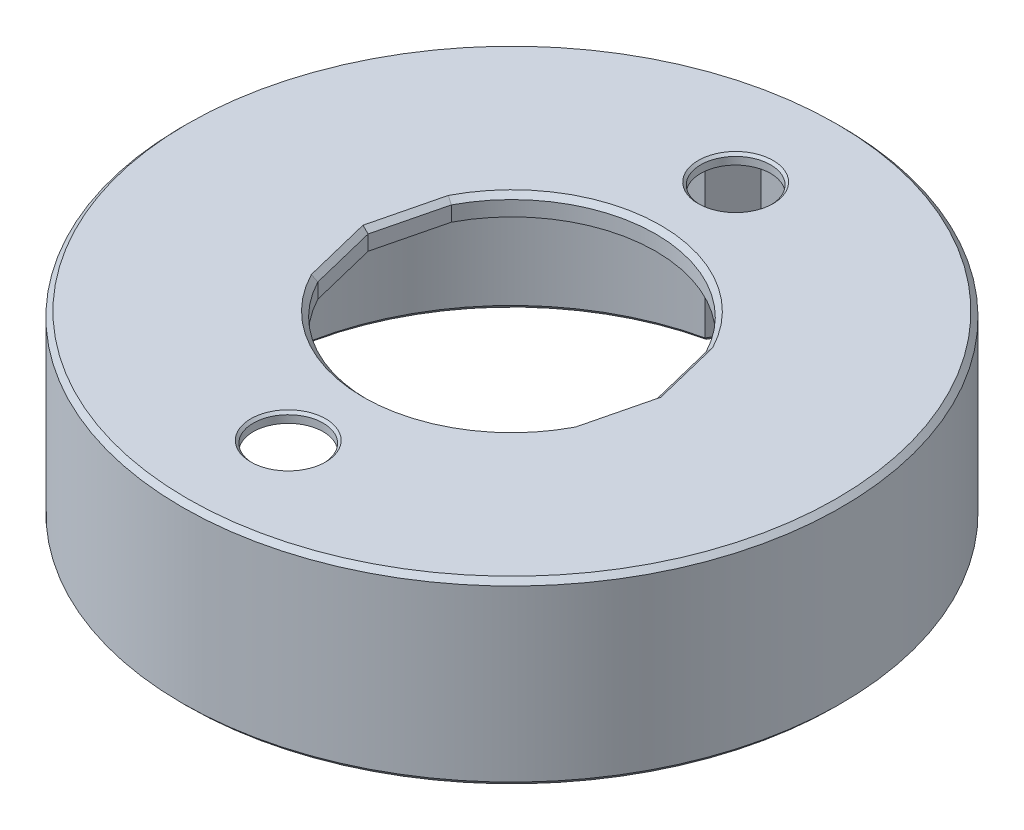
SolidWorks part; units mm, degrees
ref_plane "Front Plane" through (0, 0, 0) normal (0, 0, 1) x (1, 0, 0)
ref_plane "Top Plane" through (0, 0, 0) normal (0, 1, 0) x (1, 0, 0)
ref_plane "Right Plane" through (0, 0, 0) normal (1, 0, 0) x (0, 0, -1)
sketch "Sketch1" plane through (0, 0, 0) normal (0, 1, 0) x (1, 0, 0)
  circle A0 centre (0, 0) radius 12.73
  circle A1 centre (0, 0) radius 16.5
  dimension "D1" = 3.77
  dimension "D2" = 33
extrude "Boss-Extrude1" add sketch "Sketch1" along normal blind 8
sketch "Sketch2" plane through (0, 8, 0) normal (0, 1, 0) x (1, 0, 0)
  circle A0 centre (0, 0) radius 16.5
extrude "Boss-Extrude2" add sketch "Sketch2" along normal blind 1
sketch "Sketch3" plane through (0, 9, 0) normal (0, 1, 0) x (1, 0, 0)
  line L0 (0, 13) -> (0, 11.2)
  line L1 (0, -13) -> (0, -11.2)
  line L2 (0, -13) -> (4, -13)
  line L3 (0, -13) -> (-4, -13)
  line L4 (0, 13) -> (-4, 13)
  line L5 (0, 13) -> (4, 13)
  line L6 (-7.2, 0) -> (-4, -13)
  line L7 (7.2, 0) -> (4, -13)
  line L8 (-4, 13) -> (-7.2, 0)
  line L9 (4, 13) -> (7.2, 0)
  circle A0 centre (0, 0) radius 7.2
  circle A4 centre (0, 11.2) radius 1.75
  circle A5 centre (0, -11.2) radius 1.75
  dimension "D1" = 14.4
  dimension "D7" = 1.8
  dimension "D8" = 3.5
  dimension "D9" = 1.8
  dimension "D10" = 3.5
  dimension "D2" = 13
  dimension "D3" = 13
  dimension "D4" = 4
  dimension "D5" = 4
  dimension "D6" = 4
extrude "Cut-Extrude1" cut sketch "Sketch3" against normal blind 12 contours L9 A0 L8 L6 L7 | A4 | A5 region at (1.2024, 9, -12.4024) region at (0, 9, 0) region at (-1.2024, 9, 9.9976)
sketch "Sketch4" plane through (0, 8, 0) normal (0, -1, 0) x (1, 0, 0)
  line L1 (3.4641, 11.2) -> (1.7321, 14.2)
  line L2 (1.7321, 14.2) -> (-1.7321, 14.2)
  line L3 (-1.7321, 14.2) -> (-3.4641, 11.2)
  line L4 (-3.4641, 11.2) -> (-1.7321, 8.2)
  line L5 (-1.7321, 8.2) -> (1.7321, 8.2)
  line L6 (1.7321, 8.2) -> (3.4641, 11.2)
  circle A0 centre (0, 11.2) radius 3 construction
  dimension "D1" = 6
extrude "Cut-Extrude2" cut sketch "Sketch4" along normal blind 12
sketch "Sketch5" plane through (0, 8, 0) normal (0, -1, 0) x (1, 0, 0)
  line L1 (3.4416, 11.2) -> (1.7208, 14.1806)
  line L2 (1.7208, 14.1806) -> (-1.7208, 14.1806)
  line L3 (-1.7208, 14.1806) -> (-3.4416, 11.2)
  line L4 (-3.4416, 11.2) -> (-1.7208, 8.2194)
  line L5 (-1.7208, 8.2194) -> (1.7208, 8.2194)
  line L6 (1.7208, 8.2194) -> (3.4416, 11.2)
  circle A0 centre (0, 11.2) radius 2.9806 construction
extrude "Cut-Extrude3" cut sketch "Sketch5" against normal blind 0.5
sketch "Sketch6" plane through (0, 8, 0) normal (0, -1, 0) x (1, 0, 0)
  line L1 (3.4641, -11.2) -> (1.7321, -8.2)
  line L2 (1.7321, -8.2) -> (-1.7321, -8.2)
  line L3 (-1.7321, -8.2) -> (-3.4641, -11.2)
  line L4 (-3.4641, -11.2) -> (-1.7321, -14.2)
  line L5 (-1.7321, -14.2) -> (1.7321, -14.2)
  line L6 (1.7321, -14.2) -> (3.4641, -11.2)
  circle A0 centre (0, -11.2) radius 3 construction
  dimension "D1" = 6
extrude "Cut-Extrude4" cut sketch "Sketch6" along normal blind 17.5
sketch "Sketch7" plane through (0, 8, 0) normal (0, -1, 0) x (1, 0, 0)
  line L1 (3.4876, -11.2) -> (1.7438, -8.1797)
  line L2 (1.7438, -8.1797) -> (-1.7438, -8.1797)
  line L3 (-1.7438, -8.1797) -> (-3.4876, -11.2)
  line L4 (-3.4876, -11.2) -> (-1.7438, -14.2203)
  line L5 (-1.7438, -14.2203) -> (1.7438, -14.2203)
  line L6 (1.7438, -14.2203) -> (3.4876, -11.2)
  circle A0 centre (0, -11.2) radius 3.0203 construction
extrude "Cut-Extrude5" cut sketch "Sketch7" against normal blind 0.5
chamfer "Chamfer1" distance 0.25 angle 45 7 edges at (-6.7887, 9, 1.6711) (-6.7887, 9, -1.6711) (0, 9, -7.2) (6.7887, 9, -1.6711) (6.7887, 9, 1.6711) (0, 9, 7.2) (0, 9, 16.5)
chamfer "Chamfer2" distance 0.125 angle 45 2 edges at (0, 9, -9.45) (0, 9, 12.95)
chamfer "Chamfer3" distance 0.25 angle 45 8 edges at (2.2435, 0, -13.3142) (0, 0, -14.2) (-2.2435, 0, -13.3142) (-12.73, 0, 0) (-2.2435, 0, 13.3142) (0, 0, 14.2) (2.2435, 0, 13.3142) (12.73, 0, 0)
chamfer "Chamfer4" distance 0.25 angle 45 1 edges at (0, 0, 16.5)
